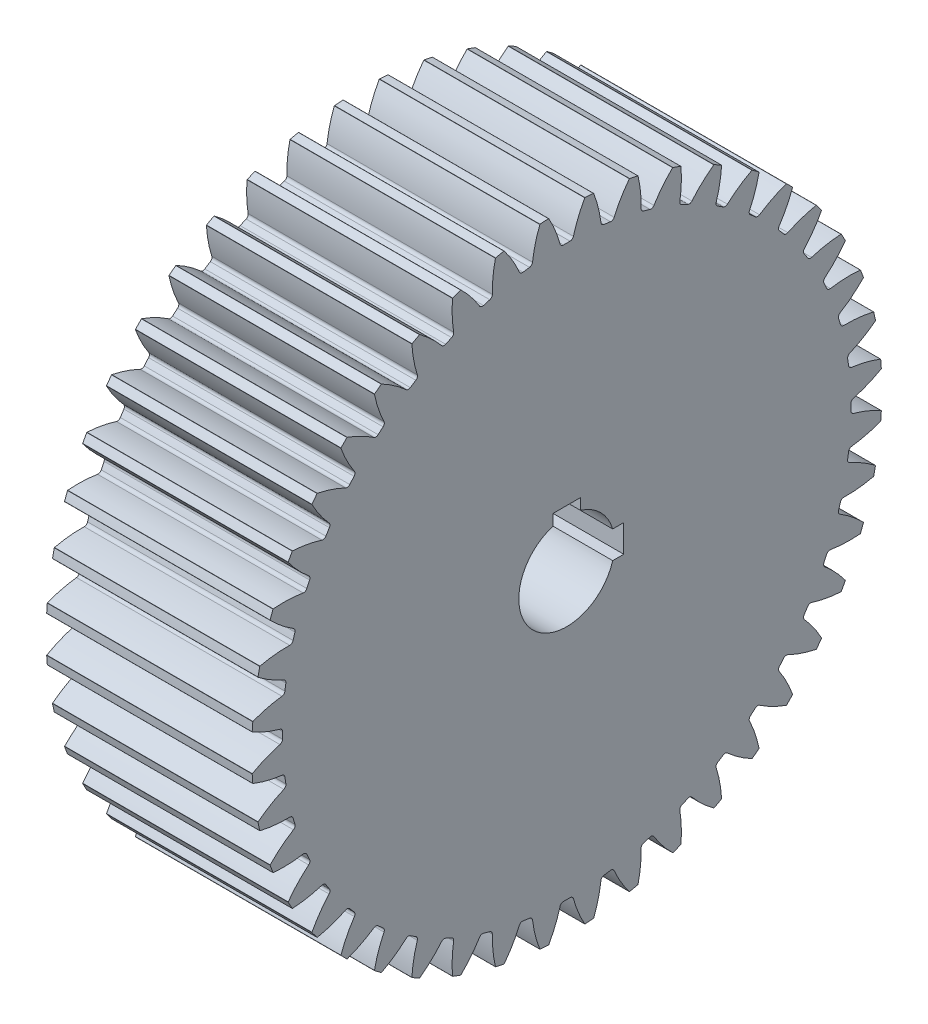
SolidWorks part; units mm, degrees
material "Aluminum Bronze"
ref_plane "Plane1" through (0, 0, 0) normal (0, 0, 1) x (1, 0, 0)
ref_plane "Plane2" through (0, 0, 0) normal (0, 1, 0) x (1, 0, 0)
ref_plane "Plane3" through (0, 0, 0) normal (1, 0, 0) x (0, 0, -1)
sketch "HoldingSke" plane through (0, 0, 0) normal (0, 1, 0) x (1, 0, 0)
  line L0 (0, 0) -> (0.1439, -0.1389)
  line L1 (-15, 0) -> (100, 0) construction
  line L2 (0, 0) -> (-2.1039, 2.3779)
  line L3 (0, 0) -> (-11.863, 4.5341)
  line L4 (0, 0) -> (6.2122, 5.9991)
  line L5 (0, 0) -> (-70.2715, -26.2092)
  line L6 (0, 0) -> (-62.1722, -41.9478)
  line L7 (-2.1039, 2.3779) -> (14.0409, 75.6248)
  line L8 (-76.2, 54.61) -> (-72.9, 54.61)
  line L9 (-71.009, 38.7566) -> (-53.1078, 45.2721)
  line L10 (-76.2, 71.12) -> (104.1128, 71.12)
  line L11 (0, 0) -> (-75, 0)
  line L12 (-76.2, 101.6) -> (-76.033, 101.6)
  line L13 (24.9733, 27.94) -> (52.9518, 28.4284)
  line L14 (24.9733, 27.94) -> (24.9743, 27.94)
  line L15 (24.9733, 27.94) -> (100.4006, 29.5858)
  line L16 (-63.627, -5) -> (-12.827, -5)
  circle A0 centre (0, 0) radius 17.5
  circle A1 centre (0, 0) radius 37.5
  circle A2 centre (0, 0) radius 37.5
  circle A3 centre (0, 0) radius 17.5
  dimension "Num_teeth" = 44
  dimension "Pitch_radius" = 180.3128
  dimension "Width" = 75
  dimension "Thickness" = 75
sketch "BasProSke" plane through (0, 0, 0) normal (0, 1, 0) x (1, 0, 0)
  line L0 (-10, 0) -> (60, 0) construction
  line L1 (0, 0) -> (0, 115)
  line L2 (0, 0) -> (75, 0)
  line L3 (75, 0) -> (75, 115)
  line L4 (75, 115) -> (0, 115)
  dimension "Thickness" = 75
  dimension "Diameter" = 230
revolve "Base-Revolve" add sketch "BasProSke" angle 360 about L0
sketch "TooCutSke" plane through (0, 0, 0) normal (1, 0, 0) x (0, 0, -1)
  line L1 (0, 0) -> (0, 107) construction
  line L2 (0, 0) -> (-4.2184, 109.9191) construction
  line L3 (0, 0) -> (-15.6861, 219.3197) construction
  line L4 (-4.2184, 109.9191) -> (-7.843, 109.6598) construction
  arc A0 (2.1815, 103.7261) -> (-2.1815, 103.7261) centre (0, 0) ccw
  arc A1 (6.6179, 114.8349) -> (-6.6179, 114.8349) centre (0, 0) ccw
  circle A2 centre (0, 0) radius 110 construction
  circle A3 centre (0, 0) radius 103.3662 construction
  arc A4 (-2.1815, 103.7261) -> (-6.6179, 114.8349) centre (-44.8825, 93.1135) ccw
  arc A5 (6.6179, 114.8349) -> (2.1815, 103.7261) centre (44.8825, 93.1135) ccw
extrude "ToothCut" cut sketch "TooCutSke" along normal through all
fillet "Breaks" radius 0.1 2 edges at (37.5, 114.8102, -6.6039) (37.5, 114.8102, 6.6039) tangent propagation no
fillet "RootFillets" radius 1.251 2 edges at (37.5, 103.7261, -2.1815) (37.5, 103.7261, 2.1815)
pattern_circular "TeethCuts" count 44 every 8.182 about axis through (-10, 0, 0) along (1, 0, 0) of "ToothCut", "RootFillets", "Breaks"
sketch "HubNeaOneSke" plane through (0, 0, 0) normal (-1, 0, 0) x (0, 0, 1)
  circle A0 centre (0, 0) radius 37.5
  dimension "Diameter" = 75
extrude "HubNearOne" [suppressed] add sketch "HubNeaOneSke" along normal blind 0.0051
sketch "HubNeaBotSke" plane through (0, 0, 0) normal (-1, 0, 0) x (0, 0, 1)
  circle A0 centre (0, 0) radius 37.5
  dimension "Diameter" = 75
extrude "HubNearBoth" [suppressed] add sketch "HubNeaBotSke" along normal blind 0.0026
ref_plane "FarPln" through (75, 0, 0) normal (1, 0, 0) x (0, 0, -1)
sketch "HubFarSke" plane through (75, 0, 0) normal (1, 0, 0) x (0, 0, -1)
  circle A0 centre (0, 0) radius 37.5
  dimension "Diameter" = 75
extrude "HubFar" [suppressed] add sketch "HubFarSke" along normal blind 0.0026
sketch "BorSke" plane through (0, 0, 0) normal (1, 0, 0) x (0, 0, -1)
  circle A0 centre (0, 0) radius 17.5
  dimension "Diameter" = 35
extrude "Bore" cut sketch "BorSke" along normal mid plane 150.0103
sketch "KeySke" plane through (0, 0, 0) normal (1, 0, 0) x (0, 0, -1)
  line L0 (-5, 0) -> (-5, 20.8)
  line L1 (-5, 20.8) -> (5, 20.8)
  line L2 (5, 20.8) -> (5, 0)
  line L3 (0, 0) -> (0, 34) construction
  line L4 (-5, 0) -> (5, 0)
  dimension "Width" = 10
extrude "Keyway" cut sketch "KeySke" along normal mid plane 150.0103
pattern_circular "Keyway2" count 2 every 90 about axis through (-10, 0, 0) along (1, 0, 0) of "Keyway" reverse direction yes
scale "Scale1" [suppressed]
ref_axis "Axis1" through (75, 0, 0) along (-1, 0, 0)
sketch "Sketch1" plane through (0, 0, 0) normal (0, 1, 0) x (1, 0, 0)
  line L0 (75, 25.9487) -> (0, 25.9487) construction
  line L1 (-17.8331, 63.9487) -> (22.181, 63.9487)
  line L2 (-17.8331, 63.9487) -> (-17.8331, 25.9487)
  line L3 (-17.8331, 25.9487) -> (22.181, 25.9487)
  line L4 (32.1669, 53.9628) -> (32.1669, 35.9346)
  line L5 (-17.8331, 63.9487) -> (32.1669, 25.9487) construction
  line L6 (-17.8331, 25.9487) -> (32.1669, 63.9487) construction
  arc A0 (32.1669, 35.9346) -> (22.181, 25.9487) centre (22.181, 35.9346) cw
  arc A1 (32.1669, 53.9628) -> (22.181, 63.9487) centre (22.181, 53.9628) ccw
  point P0 (7.1669, 44.9487)
  dimension "D3" = 9.9859
  dimension "D1" = 38
  dimension "D2" = 50
revolve "Cut-Revolve1" cut sketch "Sketch1" angle 360 about axis through (75, 0, 0) along (-1, 0, 0)
equation "' \"Module@HoldingSke\" = 6.35"
equation "' \"Num_teeth@HoldingSke\" = 12"
equation "' \"Ap@HoldingSke\" =  20"
equation "' \"Ap@HoldingSke\" = 20"
equation "' \"Width@HoldingSke\" = 0.5 * 25.4"
equation "' \"Hub_dia@HoldingSke\"= 1 * 25.4"
equation "' \"Hub_dia@HoldingSke\" = 1 * 25.4"
equation "' \"Overall_len@HoldingSke\" = 1.0 * 25.4"
equation "' \"Bore@HoldingSke\" = 0.75 * 25.4"
equation "' \"T_dim@HoldingSke\" = 0.1 * 25.4"
equation "' \"Width@KeySke\" = 0.25 * 25.4"
equation "' \"Show_teeth@HoldingSke\" = 13"
equation "' \"Backlash@HoldingSke\" = 0.009 * 25.4"
equation "' \"Addendum_fac@HoldingSke\" = 1.0"
equation "' \"Dedendum_fac@HoldingSke\" = 1.25"
equation "' \"Dedendum_add@HoldingSke\" = 0.00005 * 25.4"
equation "' \"Clearance_fac@HoldingSke\" = 0.25"
equation "\"Pitch@HoldingSke\" = 1 / \"Module@HoldingSke\""
equation "\"Overcut_dia@TooCutSke\" = (\"Num_teeth@HoldingSke\" + 2 * \"Addendum_fac@HoldingSke\") / \"Pitch@HoldingSke\" + 0.002 * 25.4"
equation "\"Pitch_dia@TooCutSke\" = \"Num_teeth@HoldingSke\" / \"Pitch@HoldingSke\""
equation "\"Base_dia@TooCutSke\" = \"Num_teeth@HoldingSke\" / \"Pitch@HoldingSke\" * cos((\"Ap@HoldingSke\"  * 3.14159265 / 180))"
equation "\"Root_dia@TooCutSke\" = (\"Num_teeth@HoldingSke\" + 2) / \"Pitch@HoldingSke\" - 2 * (\"Addendum_fac@HoldingSke\" + \"Dedendum_fac@HoldingSke\") / \"Pitch@HoldingSke\" - \"Dedendum_add@HoldingSke\" * 2"
equation "\"Half_ang@TooCutSke\" = 180 / \"Num_teeth@HoldingSke\""
equation "\"Half_CT@TooCutSke\" = \"Num_teeth@HoldingSke\" / \"Pitch@HoldingSke\" * sin((3.14159265 / 2 / \"Num_teeth@HoldingSke\")) / 2 - 7 * \"Backlash@HoldingSke\" / 4"
equation "\"Flank_rad@TooCutSke\" = \"Num_teeth@HoldingSke\" / \"Pitch@HoldingSke\" / 5"
equation "\"Radius@RootFillets\" = \"Clearance_fac@HoldingSke\" / \"Pitch@HoldingSke\" + \"Dedendum_add@HoldingSke\""
equation "\"Break_rad@Breaks\" = 0.02 / \"Pitch@HoldingSke\""
equation "\"Thickness@HoldingSke\" = \"Width@HoldingSke\""
equation "\"OAL@HoldingSke\" = \"Thickness@HoldingSke\""
equation "\"MHD@HoldingSke\" = (\"Num_teeth@HoldingSke\" + 2) / \"Pitch@HoldingSke\" - 2 * (\"Addendum_fac@HoldingSke\" + \"Dedendum_fac@HoldingSke\")  / \"Pitch@HoldingSke\" - \"Dedendum_add@HoldingSke\" * 2"
equation "\"MBD@HoldingSke\" = (\"Num_teeth@HoldingSke\" + 2) / \"Pitch@HoldingSke\" - 2 * (\"Addendum_fac@HoldingSke\" + \"Dedendum_fac@HoldingSke\")  / \"Pitch@HoldingSke\" - \"Dedendum_add@HoldingSke\" * 2 - 0.002 * 25.4"
equation "\"MHD@HoldingSke\" = ((sgn( \"MHD@HoldingSke\" - \"Hub_dia@HoldingSke\" )-1)*( \"MHD@HoldingSke\" - \"Hub_dia@HoldingSke\" ))/-2+ \"Hub_dia@HoldingSke\""
equation "\"MBD@HoldingSke\" = ((sgn( \"MBD@HoldingSke\" - \"Bore@HoldingSke\" )-1)*( \"MBD@HoldingSke\" - \"Bore@HoldingSke\" ))/-2+ \"Bore@HoldingSke\""
equation "\"OAL@HoldingSke\" = ((sgn( \"OAL@HoldingSke\" - \"Overall_len@HoldingSke\" )+1)*( \"OAL@HoldingSke\" - \"Overall_len@HoldingSke\" ))/2 + \"Overall_len@HoldingSke\" + 0.000002 * 25.4"
equation "\"Num_teeth@TeethCuts\" = int( \"Show_teeth@HoldingSke\" ) + 1"
equation "\"Num_teeth@TeethCuts\" = ((sgn( \"Num_teeth@TeethCuts\" - \"Num_teeth@HoldingSke\" )-1)*( \"Num_teeth@TeethCuts\" - \"Num_teeth@HoldingSke\" ))/-2+ \"Num_teeth@HoldingSke\""
equation "\"Num_teeth@TeethCuts\" = ((sgn( \"Num_teeth@TeethCuts\" - 2.0)+1)*( \"Num_teeth@TeethCuts\" - 2.0))/2 +2.0"
equation "\"Angle@TeethCuts\" = 360.0 / \"Num_teeth@HoldingSke\""
equation "\"Diameter@BasProSke\" = (\"Num_teeth@HoldingSke\" + 2 * \"Addendum_fac@HoldingSke\") / \"Pitch@HoldingSke\""
equation "\"Thickness@BasProSke\"  = \"Thickness@HoldingSke\""
equation "' \"Fillet_rad@BasProSke\" =  \"Thickness@HoldingSke\" * 0.05"
equation "' \"Fillet_rad@BasProSke\" = \"Thickness@HoldingSke\" * 0.05"
equation "\"MHD@HoldingSke\" = ((sgn( \"MHD@HoldingSke\" - \"Root_dia@TooCutSke\" )-1)*( \"MHD@HoldingSke\" - \"Root_dia@TooCutSke\" ))/-2+ \"Root_dia@TooCutSke\""
equation "\"Diameter@HubNeaOneSke\" = \"MHD@HoldingSke\""
equation "\"Length@HubNearOne\" = \"OAL@HoldingSke\" - \"Thickness@BasProSke\""
equation "\"Diameter@HubNeaBotSke\" = \"MHD@HoldingSke\""
equation "\"Length@HubNearBoth\" = ( \"OAL@HoldingSke\" - \"Thickness@BasProSke\" ) / 2.0"
equation "\"Thickness@FarPln\" = \"Thickness@BasProSke\""
equation "\"Diameter@HubFarSke\" = \"MHD@HoldingSke\""
equation "\"Length@HubFar\" = ( \"OAL@HoldingSke\" - \"Thickness@BasProSke\" ) / 2.0"
equation "\"Diameter@BorSke\" = \"MBD@HoldingSke\""
equation "\"D1@Bore\" = \"OAL@HoldingSke\" * 2.0"
equation "\"D1@Keyway\" = \"OAL@HoldingSke\" * 2.0"
equation "\"Offset@KeySke\" = \"T_dim@HoldingSke\" + \"MBD@HoldingSke\" / 2.0"
